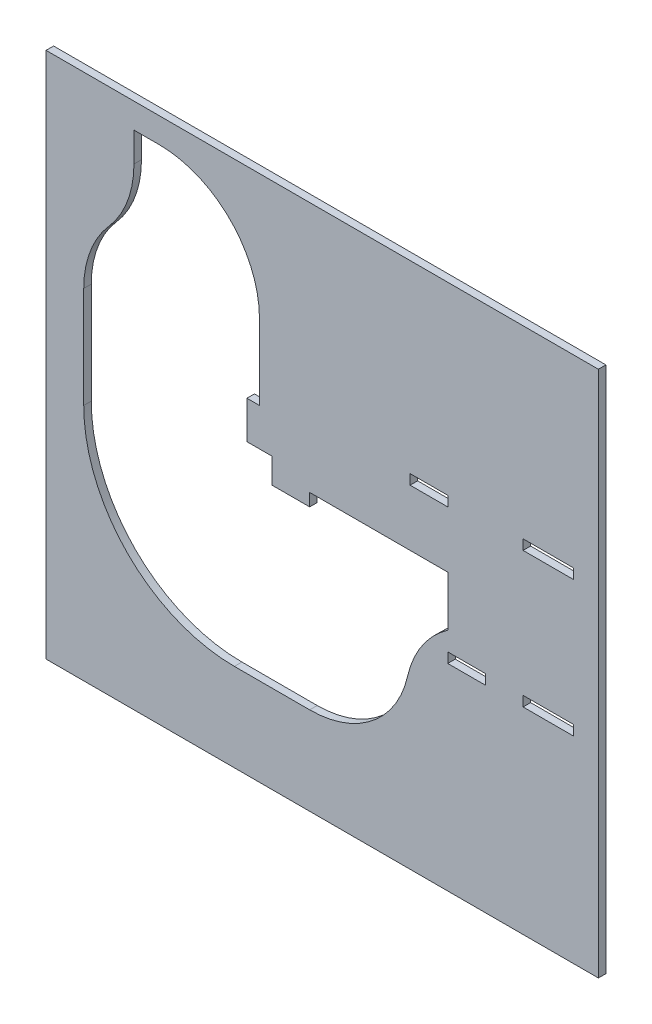
SolidWorks part; units mm, degrees
material "PBT General Purpose"
ref_plane "Front Plane" through (0, 0, 0) normal (0, 0, 1) x (1, 0, 0)
ref_plane "Top Plane" through (0, 0, 0) normal (0, 1, 0) x (1, 0, 0)
ref_plane "Right Plane" through (0, 0, 0) normal (1, 0, 0) x (0, 0, -1)
sketch "Sketch1" plane through (0, 0, 0) normal (0, 0, 1) x (1, 0, 0)
  line L1 (0, 0) -> (-19, 0)
  line L2 (0, 0) -> (0, 21) construction
  line L4 (-19, 0) -> (-19, 21)
  line L5 (-8.5, 11) -> (-3, 11)
  line L6 (-8.5, 11) -> (-8.5, 10.5)
  line L7 (-8.5, 10.5) -> (-10, 10.5)
  line L8 (-10, 10.5) -> (-10, 11.5)
  line L9 (-10, 11.5) -> (-11, 11.5)
  line L10 (-11, 11.5) -> (-11, 13)
  line L11 (-11, 13) -> (-10.5, 13)
  line L12 (-10.5, 13) -> (-10.5, 20)
  line L14 (-4.5, 3.5) -> (-17.5, 3.5)
  line L15 (-17.5, 3.5) -> (-17.5, 17)
  line L16 (-4.5, 3.5) -> (-4.5, 9)
  line L21 (-4.5, 9) -> (-3, 9)
  line L25 (-3, 11) -> (-3, 9)
  line L26 (-19, 21) -> (0, 21)
  line L27 (-10.5, 20) -> (-15.5, 20)
  line L28 (-15.5, 20) -> (-15.5, 17)
  line L29 (-15.5, 17) -> (-17.5, 17)
  line L30 (0, 0) -> (3, 0)
  line L31 (3, 0) -> (3, 21)
  line L32 (3, 21) -> (0, 21)
  dimension "D2" = 19
  dimension "D3" = 2
  dimension "D4" = 3.5
  dimension "1" = 1.5
  dimension "D5" = 1
  dimension "D6" = 1
  dimension "D7" = 21
  dimension "D8" = 4.5
  dimension "D9" = 1.5
  dimension "D10" = 1.5
  dimension "D11" = 0.5
  dimension "D12" = 0.5
  dimension "D13" = 6.5
  dimension "D14" = 5
  dimension "D15" = 1
  dimension "D16" = 6.5
  dimension "D17" = 3
  dimension "D18" = 4
  dimension "D19" = 3
extrude "Boss-Extrude1" add sketch "Sketch1" along normal mid plane 0.3
fillet "Fillet3" radius 6 1 edges at (-17.5, 3.5, 0)
fillet "Fillet4" radius 4 2 edges at (-17.5, 17, 0) (-4.5, 3.5, 0)
fillet "Fillet5" radius 4 2 edges at (-15.5, 17, 0) (-4.5, 9, 0)
fillet "Fillet7" radius 4 1 edges at (-10.5, 20, 0)
sketch "Sketch3" plane through (0, 0, 0.15) normal (0, 0, 1) x (1, 0, 0)
  line L0 (2, 8.25) -> (2, 13.25) construction
  line L1 (2, 8.25) -> (0, 8.25)
  line L2 (2, 8.25) -> (2, 7.85)
  line L3 (2, 7.85) -> (0, 7.85)
  line L4 (0, 8.25) -> (0, 7.85)
  line L5 (-1.5, 8.25) -> (-3, 8.25)
  line L6 (-1.5, 8.25) -> (-1.5, 7.85)
  line L7 (-1.5, 7.85) -> (-3, 7.85)
  line L8 (-3, 8.25) -> (-3, 7.85)
  line L9 (2, 13.65) -> (0, 13.65)
  line L10 (2, 13.65) -> (2, 13.25)
  line L11 (2, 13.25) -> (0, 13.25)
  line L12 (0, 13.65) -> (0, 13.25)
  line L13 (-3, 13.65) -> (-4.5, 13.65)
  line L14 (-3, 13.65) -> (-3, 13.25)
  line L15 (-3, 13.25) -> (-4.5, 13.25)
  line L16 (-4.5, 13.65) -> (-4.5, 13.25)
  line L18 (-11, 11.5) -> (-11, 13) construction
  line L19 (3, 0) -> (3, 21) construction
  point P18 (2, 10.75)
  point P21 (-11, 12.25)
  dimension "D1" = 0.4
  dimension "D2" = 0.4
  dimension "D3" = 2
  dimension "D4" = 1.5
  dimension "D5" = 1.5
  dimension "D6" = 5
  dimension "D7" = 1.5
  dimension "D8" = 1
  dimension "D9" = 1.5
  dimension "D10" = 3
extrude "Cut-Extrude1" cut sketch "Sketch3" against normal through all
equation "\"t\"= 0.3'thickness of the sheets"
equation "\"FlexJoint\"= 0.15'Width of flextures"
equation "\"FoldJoint\"= 0.4'Width of folding joints"
equation "\"AssembleAngle\"= 90'Angle of assembly parts"
equation "\"D1@Boss-Extrude1\"=\"t\""
